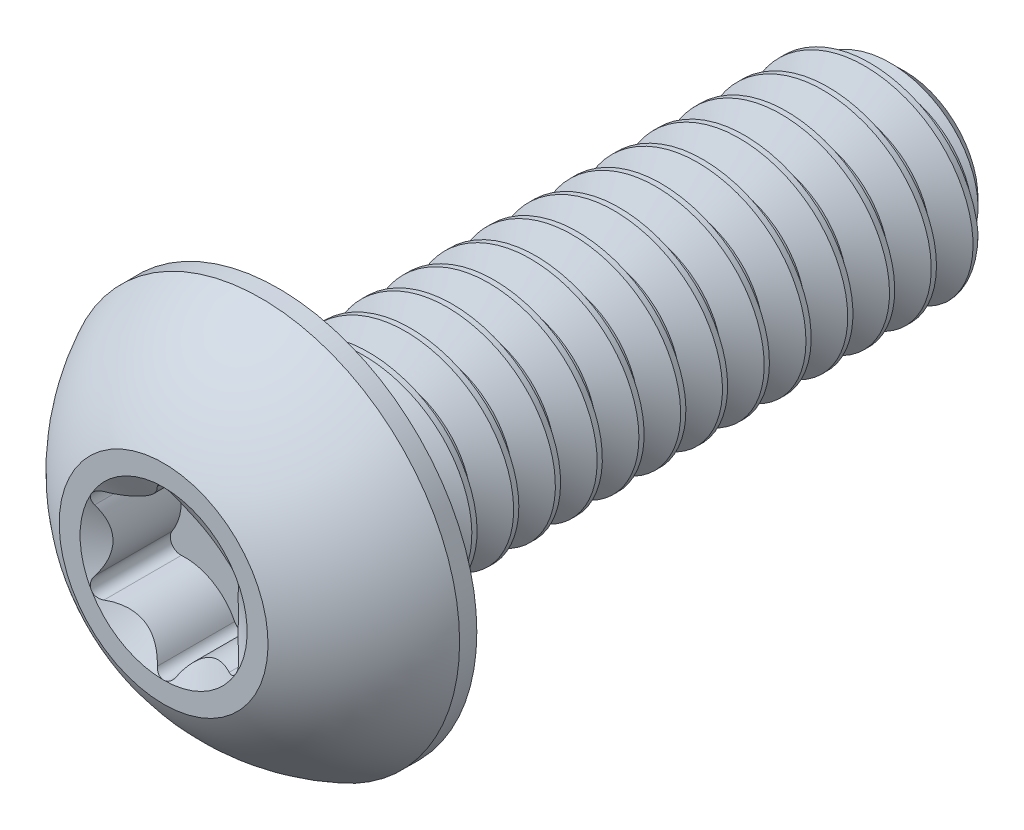
SolidWorks part; units mm, degrees
material "AISI 304"
ref_plane "Front" through (0, 0, 0) normal (0, 0, 1) x (1, 0, 0)
ref_plane "Top" through (0, 0, 0) normal (0, 1, 0) x (1, 0, 0)
ref_plane "Right" through (0, 0, 0) normal (1, 0, 0) x (0, 0, -1)
sketch "Sketch1" plane through (0, 0, 0) normal (1, 0, 0) x (0, 0, -1)
  line L2 (1.1, 1) -> (7.1, 1)
  line L3 (7.1, 1) -> (7.1, 0)
  line L4 (7.1, 0) -> (1.1, 0)
  line L6 (0.935, 1.9) -> (1.1, 1.9) construction
  line L7 (7.1, 1) -> (7.1, -1) construction
  line L8 (0, 0) -> (1.1, 0) construction
  line L9 (1.1, 1.9) -> (1.1, -1.9) construction
  line L11 (1.1, 1) -> (1.1, 0)
  line L14 (0, 0) -> (0, 1) construction
  arc A3 (0, 1) -> (0.935, 1.9) centre (1.8632, 0) cw construction
  dimension "D1" = 0.165
revolve "Revolve1" add sketch "Sketch1" angle 360 mid plane about L4
sketch "Sketch3" plane through (0, 0, -7.1) normal (0, 0, -1) x (-1, 0, 0)
  circle A0 centre (0, 0) radius 1
curve "Helix/Spiral1" pitch 0.4 height 6.4 radius 1 centre (0, 0, -7.1) axis (0, 0, 1) start towards (0, 1, 0)
sketch "Sketch2" plane through (0, 0, 0) normal (1, 0, 0) x (0, 0, -1)
  line L0 (7.1, 1) -> (7.45, 1)
  line L1 (7.45, 1) -> (7.3, 0.7402)
  line L2 (7.3, 0.7402) -> (7.25, 0.7402)
  line L3 (7.25, 0.7402) -> (7.1, 1)
  line L4 (7.175, 0.8701) -> (7.375, 0.8701) construction
  dimension "D1" = 60
  dimension "D2" = 0.05
  dimension "D3" = 0.2
chamfer "Chamfer1" distance 0.3 angle 45 1 edges at (0, 1, -7.1)
sweep "Cut-Sweep1" cut profiles "Sketch2" path "Helix/Spiral1" align with end faces yes
sketch "Sketch7" plane through (0, 0, 0) normal (1, 0, 0) x (0, 0, -1)
  line L0 (0, 0) -> (0, 1) construction
  line L6 (0.935, 1.9) -> (1.1, 1.9) construction
  line L8 (0, 0) -> (1.1, 0) construction
  line L11 (1.1, 1.9) -> (1.1, -1.9) construction
  line L12 (0.935, 1.9) -> (1.1, 1.9)
  line L13 (0, 0) -> (1.1, 0)
  line L15 (1.1, 1.9) -> (1.1, 0)
  line L16 (0, 1) -> (0, 0)
  arc A2 (0.935, 1.9) -> (0, 1) centre (1.8632, 0) ccw construction
  arc A3 (0.935, 1.9) -> (0, 1) centre (1.8632, 0) ccw
revolve "Revolve2" add sketch "Sketch7" angle 360 mid plane about L13
sketch "Sketch5" plane through (0, 0, 0) normal (0, 0, 1) x (1, 0, 0)
  line L0 (2.6125, 0) -> (-2.6125, 0) construction
  line L2 (0, 0) -> (-0.6928, 0.4)
  line L3 (0, 0) -> (-0.6928, -0.4)
  line L4 (0, 0.8) -> (0, 0.7) construction
  line L5 (0, 0.7) -> (0, 0.6) construction
  circle A0 centre (0, 0) radius 0.6 construction
  circle A1 centre (0, 0) radius 0.7 construction
  circle A2 centre (0, 0) radius 0.8 construction
  arc A3 (-0.6894, 0.2944) -> (-0.6894, -0.2944) centre (-1.1298, 0) cw
  arc A4 (-0.6894, 0.2944) -> (-0.6928, 0.4) centre (-0.6062, 0.35) cw
  arc A5 (-0.6894, -0.2944) -> (-0.6928, -0.4) centre (-0.6062, -0.35) ccw
  dimension "D4" = 1.2
  dimension "D2" = 1.6
  dimension "D1" = 30
extrude "Cut-Extrude2" cut sketch "Sketch5" against normal blind 0.77
pattern_circular "CirPattern1" count 6 over 360 of "Cut-Extrude2"
sketch "Sketch11" plane through (0, 0, 0) normal (0, 0, 1) x (1, 0, 0)
  circle A0 centre (0, 0) radius 0.8 construction
  circle A1 centre (0, 0) radius 0.8
extrude "Cut-Extrude3" cut sketch "Sketch11" against normal blind 0.77 draft 60
sketch "Sketch9" [suppressed] plane through (0, 0, -1.4986) normal (0, 0, 1) x (1, 0, 0)
  circle A2 centre (0, 0) radius 1.4224
extrude "Boss-Extrude2" [suppressed] add sketch "Sketch9" against normal offset from surface (7.0104 mm away) 31.75 up to face at (0, 0.7, -7.1)
sketch "Sketch10" plane through (0, 0, 0) normal (1, 0, 0) x (0, 0, -1)
  line L0 (7.1, 1) -> (7.1, -1) construction
  point P0 (6.5, -1)
  dimension "D1" = 0.6
equation "\"D3@Helix/Spiral1\" = \"Lg@Sketch1\" + \"D4@Helix/Spiral1\""
equation "\"D2@Sketch2\" = \"D4@Helix/Spiral1\" * .125"
equation "\"D3@Sketch2\" = \"D4@Helix/Spiral1\" * .5"
equation "\"D1@Chamfer1\" = \"D4@Helix/Spiral1\" * .75"
equation "\"D1@Cut-Extrude2\" = \"Head Ht@Sketch1\" * .7"
equation "\"D1@Sketch1\" = \"Head Ht@Sketch1\" * .15"
equation "\"D1@Sketch10\" = \"D4@Helix/Spiral1\" * 1.5"
equation "\"D1@Cut-Extrude3\" = \"D1@Cut-Extrude2\""
equation "\"D2@Sketch5\" = \"Dia@Sketch1\" * .8"
equation "\"D4@Sketch5\" = \"D2@Sketch5\" * .75"
